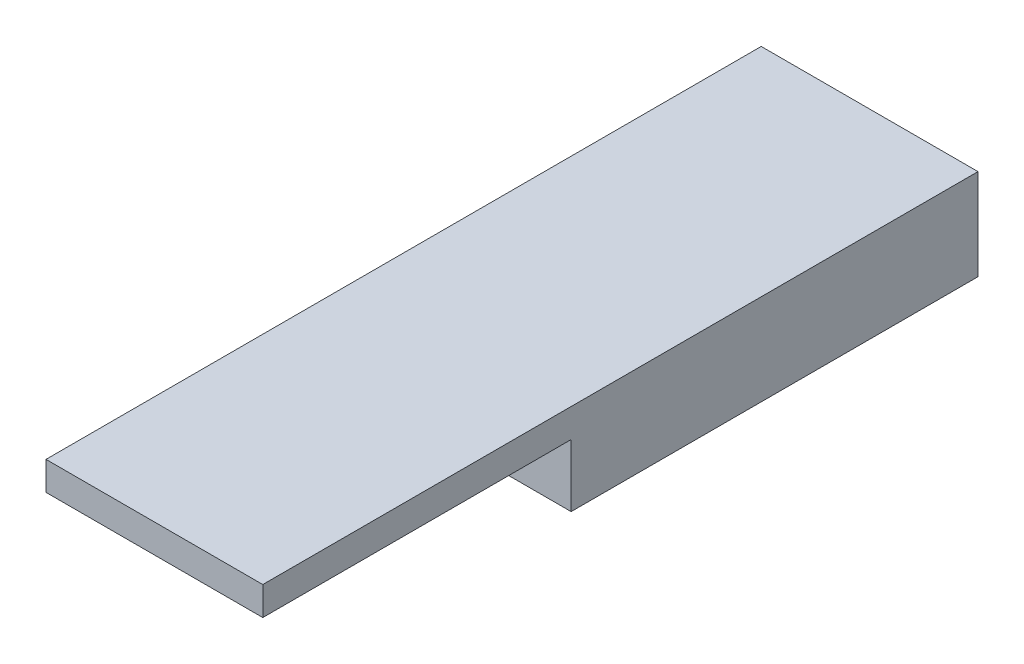
SolidWorks part; units mm, degrees
ref_plane "Front Plane" through (0, 0, 0) normal (0, 0, 1) x (1, 0, 0)
ref_plane "Top Plane" through (0, 0, 0) normal (0, 1, 0) x (1, 0, 0)
ref_plane "Right Plane" through (0, 0, 0) normal (1, 0, 0) x (0, 0, -1)
sketch "Sketch1" plane through (0, 0, 0) normal (0, 1, 0) x (1, 0, 0)
  line L5 (-6.25, 20.62) -> (6.25, 20.62)
  line L6 (-6.25, 20.62) -> (-6.25, -20.62)
  line L25 (-6.25, -20.62) -> (6.25, -20.62)
  line L26 (6.25, 20.62) -> (6.25, -20.62)
  line L27 (-6.25, 20.62) -> (6.25, -20.62) construction
  line L28 (-6.25, -20.62) -> (6.25, 20.62) construction
  line L29 (-13.97, -17.78) -> (13.97, -17.78) construction
  line L30 (0, -2.2692) -> (0, 49997.7308) construction
  line L31 (-13.97, -17.78) -> (-13.97, 17.78) construction
  line L32 (-13.97, 17.78) -> (13.97, 17.78) construction
  line L33 (13.97, -17.78) -> (13.97, 17.78) construction
  line L34 (-13.97, -17.78) -> (13.97, 17.78) construction
  line L35 (-13.97, 17.78) -> (13.97, -17.78) construction
  point P0 (0, 0)
  point P1 (0, 0)
  point P6 (0, 0)
  point P10 (0, 0)
  point P11 (0, 0)
  dimension "D4" = 35.56
  dimension "D1" = 41.24
  dimension "D2" = 12.5
  dimension "D3" = 27.94
extrude "Boss-Extrude1" add sketch "Sketch1" along normal blind 5.25 contours L5 L25 | L26 L5 L6 L25 region at (0, 0, 0)
sketch "Sketch2" plane through (0, 0, 0) normal (0, 1, 0) x (1, 0, 0)
  line L0 (6.25, 20.62) -> (6.25, -20.62) construction
  line L1 (-6.25, -2.84) -> (6.25, -2.84)
  line L2 (-6.25, -2.84) -> (-6.25, -20.62)
  line L3 (-6.25, -20.62) -> (6.25, -20.62)
  line L4 (6.25, -2.84) -> (6.25, -20.62)
  point P7 (-5.6353, -0.5404)
  point P8 (0, 0)
  dimension "D1" = 17.78
extrude "Cut-Extrude1" cut sketch "Sketch2" along normal blind 3.6
